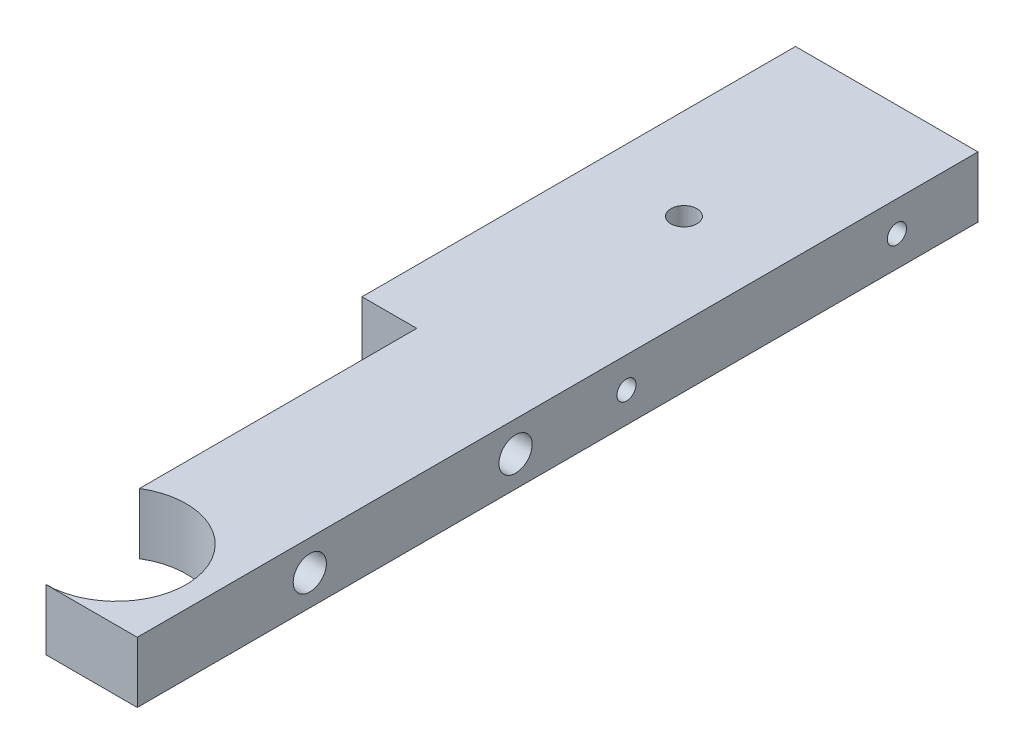
SolidWorks part; units mm, degrees
ref_plane "Front Plane" through (0, 0, 0) normal (0, 0, 1) x (1, 0, 0)
ref_plane "Top Plane" through (0, 0, 0) normal (0, 1, 0) x (1, 0, 0)
ref_plane "Right Plane" through (0, 0, 0) normal (1, 0, 0) x (0, 0, -1)
sketch "Sketch2" plane through (0, 0, 0) normal (0, 1, 0) x (1, 0, 0)
  line L0 (0, 0) -> (0, 152.4)
  line L1 (0, 152.4) -> (28.575, 152.4)
  line L2 (28.575, 152.4) -> (28.575, 0)
  line L3 (28.575, 0) -> (0, 0)
  dimension "D1" = 152.4
  dimension "D2" = 28.575
extrude "Boss-Extrude1" add sketch "Sketch2" along normal blind 9.525
sketch "Sketch3" plane through (0, 0, 0) normal (-1, 0, 0) x (0, 0, 1)
  line L3 (-152.4, 9.525) -> (0, 9.525) construction
  line L4 (-152.4, 9.525) -> (-152.4, 0) construction
  point P6 (-139.7, 4.7625)
  point P14 (-139.7, 4.7625)
  dimension "D1" = 4.7625
  dimension "D2" = 12.7
sketch "Sketch8" plane through (0, 0, 0) normal (-1, 0, 0) x (0, 0, 1)
  point P0 (-139.7, 4.7625)
hole_wizard "Ø3.0mm Dowel Hole1" positions "Sketch8" profile "Sketch9" hole size "Ø3.0" standard "ANSI Metric" end condition through all
sketch "Sketch9" plane through (0, 4.7625, -139.7) normal (0, 1, 0) x (0, 0, 1)
  line L0 (0, 0) -> (0, 28.575)
  line L1 (0, 28.575) -> (1.5, 28.575)
  line L2 (1.5, 28.575) -> (1.5, 0)
  line L5 (1.5, 0) -> (0, 0)
  line L11 (0, -6.35) -> (0, 107.95) construction
  dimension "Thru Hole Dia." = 3
  dimension "Thru Hole Depth" = 28.575
pattern_linear "LPattern1" count 4 spacing 42.3333 along (0, 0, 1) skipping (2, 0) of "Ø3.0mm Dowel Hole1"
sketch "Sketch12" plane through (0, 9.525, 0) normal (0, 1, 0) x (1, 0, 0)
  line L0 (28.575, 0) -> (28.575, 152.4) construction
  line L2 (0, 0) -> (28.575, 0) construction
  circle A1 centre (14.2875, 31.75) radius 10.975
  circle A2 centre (14.2875, 120.65) radius 2.05
  point P0 (14.2875, 120.65)
  point P1 (14.2875, 76.2)
  point P2 (14.2875, 31.75)
  dimension "D8" = 4.1
  dimension "D9" = 21.95
  dimension "D1" = 14.2875
  dimension "D2" = 14.2875
  dimension "D3" = 14.2875
  dimension "D4" = 76.2
  dimension "D5" = 44.45
  dimension "D6" = 44.45
sketch "Sketch13" plane through (0, 0, 0) normal (-1, 0, 0) x (0, 0, 1)
  line L2 (0, 9.525) -> (0, 0) construction
  line L3 (-152.4, 9.525) -> (0, 9.525) construction
  circle A0 centre (-80, 4.7625) radius 2.6
  circle A1 centre (-47.79, 4.7625) radius 2.6
  point P5 (-80, 4.7625)
  point P11 (-47.79, 4.7625)
  dimension "D1" = 80
  dimension "D2" = 4.7625
  dimension "D3" = 32.21
extrude "Cut-Extrude1" cut sketch "Sketch12" against normal through all contours A2
extrude "Cut-Extrude2" cut sketch "Sketch12<4>" against normal blind 4 contours A1
sketch "Sketch12<4>" plane through (0, 9.525, 0) normal (0, 1, 0) x (1, 0, 0) same geometry as "Sketch12"
sketch "Sketch15" plane through (0, 5.525, 0) normal (0, 1, 0) x (1, 0, 0)
  circle A0 centre (14.2875, 31.75) radius 2.5
  dimension "D1" = 5
extrude "Cut-Extrude3" cut sketch "Sketch15" against normal through all
extrude "Cut-Extrude4" cut sketch "Sketch13" against normal through all
sketch "Sketch17" plane through (0, 0, 0) normal (-1, 0, 0) x (0, 0, 1)
  line L0 (-152.4, 9.525) -> (0, 9.525) construction
  line L1 (-84.535, 9.525) -> (-43.255, 9.525)
  line L2 (-84.535, 9.525) -> (-84.535, 0)
  line L3 (-84.535, 0) -> (-43.255, 0)
  line L4 (-43.255, 9.525) -> (-43.255, 0)
  line L5 (-152.4, 0) -> (0, 0) construction
  circle A3 centre (-80, 4.7625) radius 2.6 construction
  circle A4 centre (-47.79, 4.7625) radius 2.6 construction
  point P12 (-84.535, 4.7625)
  dimension "D2" = 41.28
  dimension "D1" = 32.21
  dimension "D4" = 4.535
  dimension "D3" = 4.535
extrude "Cut-Extrude5" cut sketch "Sketch17" against normal offset from surface (8.575 mm away) 20 up to face at (28.575, 4.7625, -77.4)
sketch "Sketch18" plane through (0, 9.525, 0) normal (0, 1, 0) x (1, 0, 0)
  line L0 (14.2875, 20.775) -> (28.575, 20.775)
  line L1 (28.575, 0) -> (28.575, 152.4) construction
  line L2 (8.575, 43.255) -> (8.575, 41.1211)
  line L3 (28.575, 20.775) -> (28.575, 0)
  line L4 (28.575, 0) -> (0, 0)
  line L5 (0, 0) -> (0, 43.255)
  line L6 (0, 43.255) -> (8.575, 43.255)
  circle A0 centre (14.2875, 31.75) radius 10.975 construction
  circle A1 centre (14.2875, 31.75) radius 10.975 construction
  arc A2 (14.2875, 20.775) -> (8.575, 41.1211) centre (14.2875, 31.75) cw
extrude "Cut-Extrude6" cut sketch "Sketch18" against normal blind 10
sketch "Sketch19" plane through (0, 5.525, 0) normal (0, 1, 0) x (1, 0, 0)
  circle A0 centre (14.2875, 31.75) radius 10.975
extrude "Cut-Extrude7" cut sketch "Sketch19" against normal blind 10
